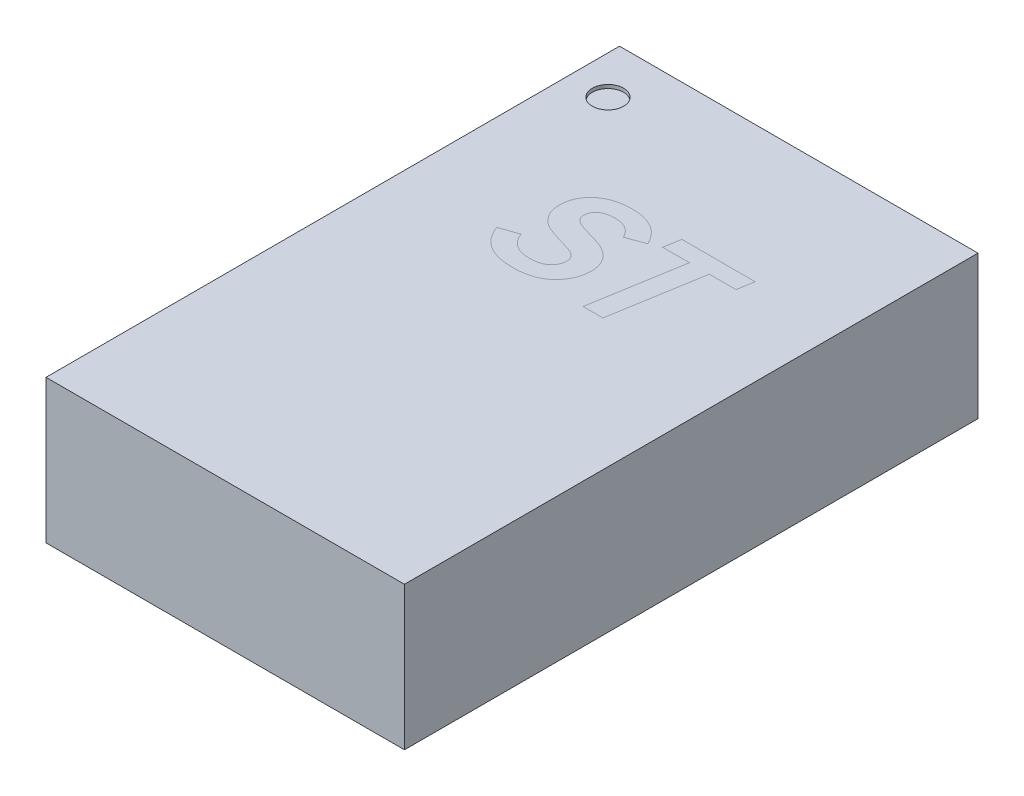
SolidWorks part; units mm, degrees
ref_plane "Спереди" through (0, 0, 0) normal (0, 0, 1) x (1, 0, 0)
ref_plane "Сверху" through (0, 0, 0) normal (0, 1, 0) x (1, 0, 0)
ref_plane "Справа" through (0, 0, 0) normal (1, 0, 0) x (0, 0, -1)
sketch "Эскиз1" plane through (0, 0, 0) normal (0, 1, 0) x (1, 0, 0)
  line L1 (-0.5, -0.8) -> (0.5, -0.8)
  line L2 (-0.5, -0.8) -> (-0.5, 0.8)
  line L3 (-0.5, 0.8) -> (0.5, 0.8)
  line L4 (0.5, -0.8) -> (0.5, 0.8)
  line L5 (-0.5, -0.8) -> (0.5, 0.8) construction
  line L6 (-0.5, 0.8) -> (0.5, -0.8) construction
  point P0 (0, 0)
  dimension "D1" = 1
  dimension "D2" = 1.6
extrude "Бобышка-Вытянуть1" add sketch "Эскиз1" along normal blind 0.4
sketch "Эскиз2" plane through (0, 0.4, 0) normal (0, 1, 0) x (1, 0, 0)
  circle A0 centre (-0.3928, 0.6606) radius 0.0436
extrude "Вырез-Вытянуть1" cut sketch "Эскиз2" against normal blind 0.01
sketch "Эскиз3" plane through (0, 0, 0) normal (0, -1, 0) x (1, 0, 0)
  line L0 (-0.5, -0.8) -> (-0.5, 0.8) construction
  line L1 (-0.35, -0.487) -> (-0.15, -0.487)
  line L2 (-0.35, -0.487) -> (-0.35, -0.687)
  line L3 (-0.35, -0.687) -> (-0.15, -0.687)
  line L4 (-0.15, -0.487) -> (-0.15, -0.687)
  line L5 (-0.35, -0.487) -> (-0.15, -0.687) construction
  line L6 (-0.35, -0.687) -> (-0.15, -0.487) construction
  line L7 (0, -1000) -> (0, 49000) construction
  line L8 (0.15, -0.487) -> (0.15, -0.687)
  line L9 (0.15, -0.487) -> (0.35, -0.487)
  line L10 (0.35, -0.487) -> (0.35, -0.687)
  line L11 (0.15, -0.687) -> (0.35, -0.687)
  line L12 (0.15, 0.103) -> (0.15, -0.097)
  line L13 (0.15, 0.103) -> (0.35, 0.103)
  line L14 (0.35, 0.103) -> (0.35, -0.097)
  line L15 (0.15, -0.097) -> (0.35, -0.097)
  line L16 (0.15, 0.693) -> (0.15, 0.493)
  line L17 (0.15, 0.693) -> (0.35, 0.693)
  line L18 (0.35, 0.693) -> (0.35, 0.493)
  line L19 (0.15, 0.493) -> (0.35, 0.493)
  line L20 (-0.35, 0.103) -> (-0.35, -0.097)
  line L21 (-0.35, 0.103) -> (-0.15, 0.103)
  line L22 (-0.15, 0.103) -> (-0.15, -0.097)
  line L23 (-0.35, -0.097) -> (-0.15, -0.097)
  line L24 (-0.35, 0.693) -> (-0.35, 0.493)
  line L25 (-0.35, 0.693) -> (-0.15, 0.693)
  line L26 (-0.15, 0.693) -> (-0.15, 0.493)
  line L27 (-0.35, 0.493) -> (-0.15, 0.493)
  line L28 (0.5, -0.8) -> (-0.5, -0.8) construction
  point P0 (-0.25, -0.587)
  dimension "D1" = 0.2
  dimension "D2" = 0.25
  dimension "D5" = 0.213
  dimension "D3" = 2
  dimension "D4" = 3
extrude "Бобышка-Вытянуть2" add sketch "Эскиз3" along normal blind 0.01
sketch "Sketch1" plane through (0, 0.4, 0) normal (0, 1, 0) x (1, 0, 0)
  line L0 (-0.5, 0.1202) -> (0.5, 0.1202) construction
  line L1 (-0.5, 0.8) -> (-0.5, -0.8) construction
  line L2 (0.5, -0.8) -> (0.5, 0.8) construction
  text T0 "ST" font "Franklin Gothic Medium" height 0.3
wrap "Wrap1" sketch "Sketch1" wrap type scribe source sketch "Sketch1"
